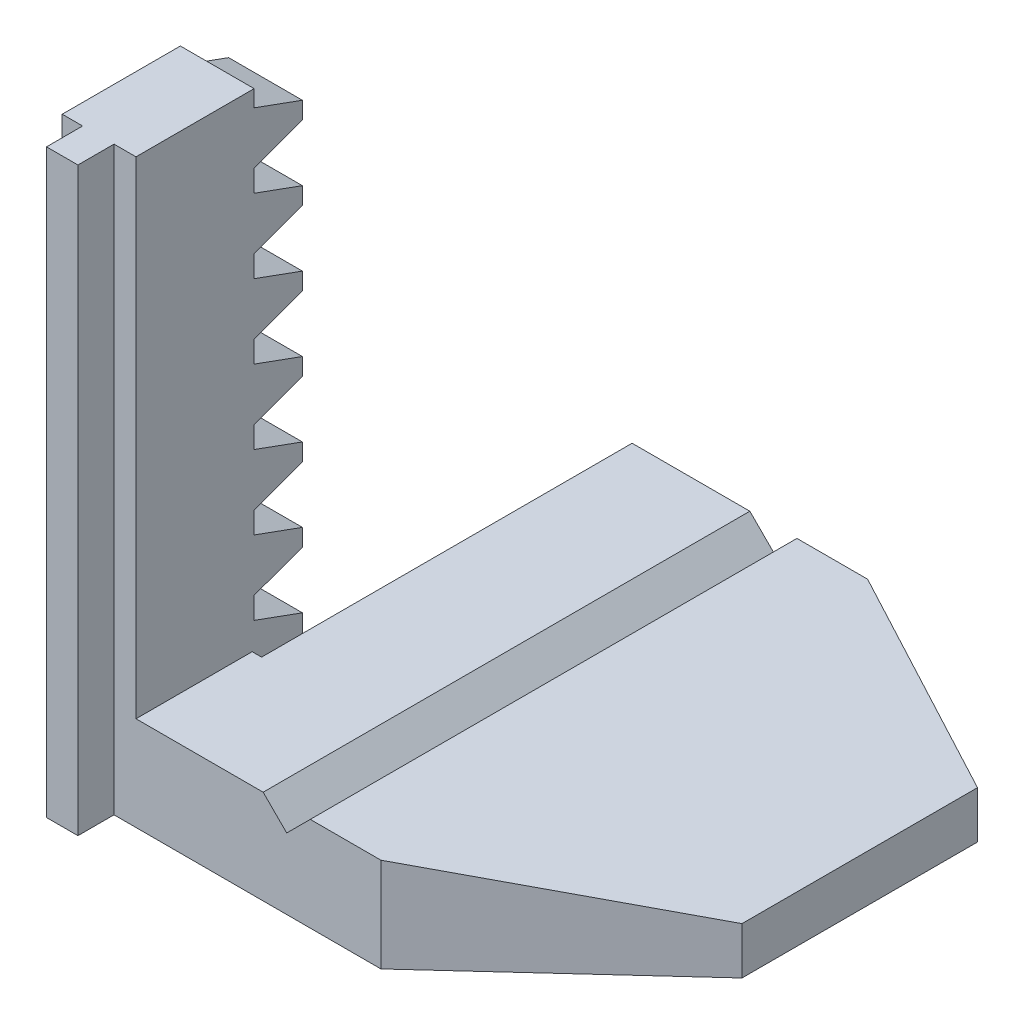
SolidWorks part; units mm, degrees
ref_plane "Front Plane" through (0, 0, 0) normal (0, 0, 1) x (1, 0, 0)
ref_plane "Top Plane" through (0, 0, 0) normal (0, 1, 0) x (1, 0, 0)
ref_plane "Right Plane" through (0, 0, 0) normal (1, 0, 0) x (0, 0, -1)
ref_plane "Plane1" through (209.7, 0, 0) normal (1, 0, 0) x (0, 0, -1)
ref_plane "Plane2" through (211, 0, 0) normal (1, 0, 0) x (0, 0, -1)
ref_plane "Plane3" through (214.4, 0, 0) normal (1, 0, 0) x (0, 0, -1)
ref_plane "Plane4" through (215, 0, 0) normal (1, 0, 0) x (0, 0, -1)
sketch "Sketch1" plane through (209.7, 0, 0) normal (1, 0, 0) x (0, 0, -1)
  line L0 (-318, -6) -> (-318, 31)
  line L1 (-318, 31) -> (-310.475, 31)
  line L2 (-310.475, 31) -> (-310.475, 30.0599)
  line L3 (-310.475, 30.0599) -> (-307.4, 28.9407)
  line L4 (-307.4, 28.9407) -> (-307.4, 27.608)
  line L5 (-307.4, 27.608) -> (-310.475, 26.4888)
  line L6 (-310.475, 26.4888) -> (-310.475, 25.3475)
  line L7 (-310.475, 25.3475) -> (-307.4, 24.2283)
  line L8 (-307.4, 24.2283) -> (-307.4, 22.8956)
  line L9 (-307.4, 22.8956) -> (-310.475, 21.7764)
  line L10 (-310.475, 21.7764) -> (-310.475, 20.6351)
  line L11 (-310.475, 20.6351) -> (-307.4, 19.5159)
  line L12 (-307.4, 19.5159) -> (-307.4, 18.1832)
  line L13 (-307.4, 18.1832) -> (-310.475, 17.064)
  line L14 (-310.475, 17.064) -> (-310.475, 15.9227)
  line L15 (-310.475, 15.9227) -> (-307.4, 14.8035)
  line L16 (-307.4, 14.8035) -> (-307.4, 13.4708)
  line L17 (-307.4, 13.4708) -> (-310.475, 12.3516)
  line L18 (-310.475, 12.3516) -> (-310.475, 11.2103)
  line L19 (-310.475, 11.2103) -> (-307.4, 10.0911)
  line L20 (-307.4, 10.0911) -> (-307.4, 8.7584)
  line L21 (-307.4, 8.7584) -> (-310.475, 7.6392)
  line L22 (-310.475, 7.6392) -> (-310.475, 6.4979)
  line L23 (-310.475, 6.4979) -> (-307.4, 5.3787)
  line L24 (-307.4, 5.3787) -> (-307.4, 4.0461)
  line L25 (-307.4, 4.0461) -> (-310.475, 2.9268)
  line L26 (-310.475, 2.9268) -> (-310.475, 1.7855)
  line L27 (-310.475, 1.7855) -> (-307.4, 0.6663)
  line L28 (-307.4, 0.6663) -> (-307.4, -0.6663)
  line L29 (-307.4, -0.6663) -> (-310.475, -1.7855)
  line L30 (-310.475, -1.7855) -> (-310.475, -2.9268)
  line L31 (-310.475, -2.9268) -> (-307.4, -4.0461)
  line L32 (-307.4, -4.0461) -> (-307.4, -5.3787)
  line L33 (-307.4, -5.3787) -> (-309.1069, -6)
  line L34 (-309.1069, -6) -> (-318, -6)
extrude "Boss-Extrude1" add sketch "Sketch1" along normal blind 4.7
sketch "Sketch2" plane through (211, 0, 0) normal (1, 0, 0) x (0, 0, -1)
  line L1 (-320.3, -6) -> (-317.9, -6)
  line L2 (-320.3, -6) -> (-320.3, 31)
  line L3 (-320.3, 31) -> (-317.9, 31)
  line L4 (-317.9, -6) -> (-317.9, 31)
extrude "Boss-Extrude2" add sketch "Sketch2" along normal blind 2
sketch "Sketch3" plane through (214.4, 0, 0) normal (1, 0, 0) x (0, 0, -1)
  line L1 (-318, -6) -> (-310.6, -6)
  line L2 (-318, -6) -> (-318, 0)
  line L3 (-318, 0) -> (-310.6, 0)
  line L4 (-310.6, -6) -> (-310.6, 0)
extrude "Boss-Extrude3" add sketch "Sketch3" along normal blind 0.8
sketch "Sketch4" plane through (215, 0, 0) normal (1, 0, 0) x (0, 0, -1)
  line L1 (-318, -6) -> (-287, -6)
  line L2 (-318, -6) -> (-318, 0)
  line L3 (-318, 0) -> (-287, 0)
  line L4 (-287, -6) -> (-287, 0)
extrude "Boss-Extrude4" add sketch "Sketch4" along normal blind 30
sketch "Sketch5" plane through (0, 0, 0) normal (0, 1, 0) x (1, 0, 0)
  line L0 (228.125, -319) -> (246.5, -309.2)
  line L1 (246.5, -309.2) -> (246.5, -319)
  line L2 (246.5, -319) -> (228.125, -319)
  line L3 (228.125, -286) -> (246.5, -295.8)
  line L4 (246.5, -295.8) -> (246.5, -286)
  line L5 (246.5, -286) -> (228.125, -286)
extrude "Cut-Extrude1" cut sketch "Sketch5" along normal mid plane 13
sketch "Sketch6" plane through (0, 0, 0) normal (0, 0, 1) x (1, 0, 0)
  line L0 (227.5, -6.5) -> (246.5, -2.7)
  line L1 (246.5, -2.7) -> (246.5, -6.5)
  line L2 (246.5, -6.5) -> (227.5, -6.5)
extrude "Cut-Extrude2" cut sketch "Sketch6" along normal through all
sketch "Sketch7" plane through (0, 0, 0) normal (0, 0, 1) x (1, 0, 0)
  line L0 (222, 0.5) -> (226, 0.5)
  line L1 (226, 0.5) -> (224, -1.5)
  line L2 (224, -1.5) -> (222, 0.5)
extrude "Cut-Extrude3" cut sketch "Sketch7" along normal through all
sketch "Sketch8" plane through (209.7, 0, 0) normal (1, 0, 0) x (0, 0, -1)
  line L0 (-307, -4.1716) -> (-310.475, -2.907)
  line L1 (-310.475, -2.907) -> (-310.475, -3.047)
  line L2 (-310.475, -3.047) -> (-307, -4.3116)
  line L3 (-307, -4.3116) -> (-307, -4.1716)
  line L4 (-307, -5.2532) -> (-310.475, -6.5178)
  line L5 (-310.475, -6.5178) -> (-310.475, -6.3778)
  line L6 (-310.475, -6.3778) -> (-307, -5.1132)
  line L7 (-307, -5.1132) -> (-307, -5.2532)
  line L8 (-307, 0.5408) -> (-310.475, 1.8054)
  line L9 (-310.475, 1.8054) -> (-310.475, 1.6654)
  line L10 (-310.475, 1.6654) -> (-307, 0.4008)
  line L11 (-307, 0.4008) -> (-307, 0.5408)
  line L12 (-307, -0.5408) -> (-310.475, -1.8054)
  line L13 (-310.475, -1.8054) -> (-310.475, -1.6654)
  line L14 (-310.475, -1.6654) -> (-307, -0.4008)
  line L15 (-307, -0.4008) -> (-307, -0.5408)
  line L16 (-307, 5.2532) -> (-310.475, 6.5178)
  line L17 (-310.475, 6.5178) -> (-310.475, 6.3778)
  line L18 (-310.475, 6.3778) -> (-307, 5.1132)
  line L19 (-307, 5.1132) -> (-307, 5.2532)
  line L20 (-307, 4.1716) -> (-310.475, 2.907)
  line L21 (-310.475, 2.907) -> (-310.475, 3.047)
  line L22 (-310.475, 3.047) -> (-307, 4.3116)
  line L23 (-307, 4.3116) -> (-307, 4.1716)
  line L24 (-307, 9.9656) -> (-310.475, 11.2302)
  line L25 (-310.475, 11.2302) -> (-310.475, 11.0902)
  line L26 (-310.475, 11.0902) -> (-307, 9.8256)
  line L27 (-307, 9.8256) -> (-307, 9.9656)
  line L28 (-307, 8.884) -> (-310.475, 7.6194)
  line L29 (-310.475, 7.6194) -> (-310.475, 7.7594)
  line L30 (-310.475, 7.7594) -> (-307, 9.024)
  line L31 (-307, 9.024) -> (-307, 8.884)
  line L32 (-307, 14.678) -> (-310.475, 15.9426)
  line L33 (-310.475, 15.9426) -> (-310.475, 15.8026)
  line L34 (-310.475, 15.8026) -> (-307, 14.538)
  line L35 (-307, 14.538) -> (-307, 14.678)
  line L36 (-307, 13.5964) -> (-310.475, 12.3318)
  line L37 (-310.475, 12.3318) -> (-310.475, 12.4718)
  line L38 (-310.475, 12.4718) -> (-307, 13.7364)
  line L39 (-307, 13.7364) -> (-307, 13.5964)
  line L40 (-307, 19.3904) -> (-310.475, 20.655)
  line L41 (-310.475, 20.655) -> (-310.475, 20.515)
  line L42 (-310.475, 20.515) -> (-307, 19.2504)
  line L43 (-307, 19.2504) -> (-307, 19.3904)
  line L44 (-307, 18.3088) -> (-310.475, 17.0442)
  line L45 (-310.475, 17.0442) -> (-310.475, 17.1842)
  line L46 (-310.475, 17.1842) -> (-307, 18.4488)
  line L47 (-307, 18.4488) -> (-307, 18.3088)
  line L48 (-307, 24.1027) -> (-310.475, 25.3673)
  line L49 (-310.475, 25.3673) -> (-310.475, 25.2274)
  line L50 (-310.475, 25.2274) -> (-307, 23.9628)
  line L51 (-307, 23.9628) -> (-307, 24.1027)
  line L52 (-307, 23.0211) -> (-310.475, 21.7565)
  line L53 (-310.475, 21.7565) -> (-310.475, 21.8965)
  line L54 (-310.475, 21.8965) -> (-307, 23.1611)
  line L55 (-307, 23.1611) -> (-307, 23.0211)
  line L56 (-307, 28.8151) -> (-310.475, 30.0797)
  line L57 (-310.475, 30.0797) -> (-310.475, 29.9397)
  line L58 (-310.475, 29.9397) -> (-307, 28.6751)
  line L59 (-307, 28.6751) -> (-307, 28.8151)
  line L60 (-307, 27.7335) -> (-310.475, 26.4689)
  line L61 (-310.475, 26.4689) -> (-310.475, 26.6089)
  line L62 (-310.475, 26.6089) -> (-307, 27.8735)
  line L63 (-307, 27.8735) -> (-307, 27.7335)
extrude "Cut-Extrude4" cut sketch "Sketch8" along normal mid plane 9.4
